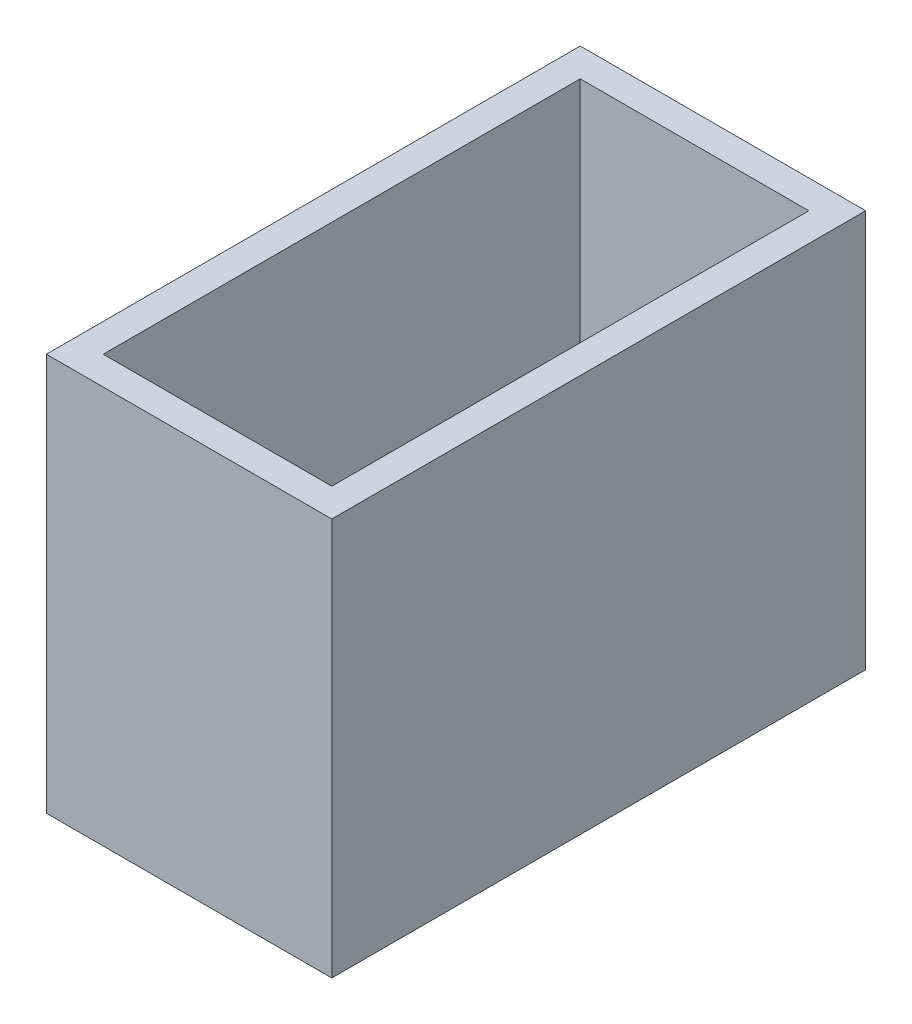
SolidWorks part; units mm, degrees
ref_plane "Front Plane" through (0, 0, 0) normal (0, 0, 1) x (1, 0, 0)
ref_plane "Top Plane" through (0, 0, 0) normal (0, 1, 0) x (1, 0, 0)
ref_plane "Right Plane" through (0, 0, 0) normal (1, 0, 0) x (0, 0, -1)
sketch "Sketch1" plane through (0, 0, 0) normal (0, 1, 0) x (1, 0, 0)
  line L0 (-5.75, 12) -> (-7.18, 12) construction
  line L1 (5.75, 12) -> (-5.75, 12)
  line L2 (5.75, 12) -> (5.75, -12)
  line L3 (5.75, -12) -> (-5.75, -12)
  line L4 (-5.75, 12) -> (-5.75, -12)
  line L5 (0, -12) -> (0, 12) construction
  line L6 (5.75, 0) -> (-5.75, 0) construction
  line L7 (7.18, 13.43) -> (-7.18, 13.43)
  line L8 (7.18, 13.43) -> (7.18, -13.43)
  line L9 (7.18, -13.43) -> (-7.18, -13.43)
  line L10 (-7.18, 13.43) -> (-7.18, -13.43)
  line L11 (0, -13.43) -> (0, 13.43) construction
  line L12 (7.18, 0) -> (-7.18, 0) construction
  line L13 (-5.75, 12) -> (-5.75, 13.43) construction
  point P0 (0, 0)
  point P4 (0, 0)
  point P8 (2.574, 5.28)
  dimension "D1" = 1.43
  dimension "D2" = 11.5
  dimension "D3" = 24
extrude "Boss-Extrude1" add sketch "Sketch1" along normal blind 20
